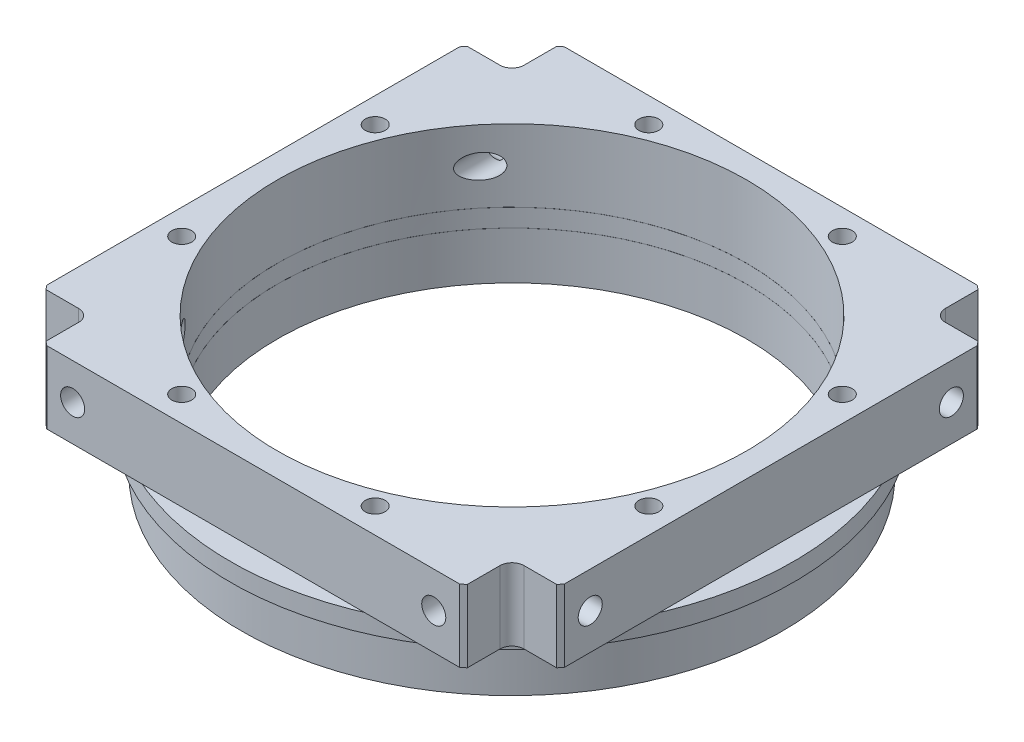
SolidWorks part; units mm, degrees
material "6061-T6 (SS)"
ref_plane "前视基准面" through (0, 0, 0) normal (0, 0, 1) x (1, 0, 0)
ref_plane "上视基准面" through (0, 0, 0) normal (0, 1, 0) x (1, 0, 0)
ref_plane "右视基准面" through (0, 0, 0) normal (1, 0, 0) x (0, 0, -1)
sketch "草图1" plane through (0, 0, 0) normal (0, 0, 1) x (1, 0, 0)
  line L0 (0, 0) -> (0, 30.5389) construction
  line L1 (-39, 0) -> (-45, 0)
  line L2 (-45, 0) -> (-45, 7.9)
  line L3 (-45, 7.9) -> (-46.8, 7.9)
  line L4 (-46.8, 7.9) -> (-46.8, 10.9)
  line L5 (-46.8, 10.9) -> (-55, 10.9)
  line L6 (-55, 10.9) -> (-55, 22.9)
  line L7 (-55, 22.9) -> (-39, 22.9)
  line L10 (-39, 22.9) -> (-39, 0)
  dimension "D1" = 90
  dimension "D2" = 78
  dimension "D3" = 7.9
  dimension "D4" = 1.8
  dimension "D5" = 3
  dimension "D6" = 110
  dimension "D9" = 12
revolve "旋转1" add sketch "草图1" angle 360 about L0
sketch "草图2" plane through (0, 22.9, 0) normal (0, 1, 0) x (1, 0, 0)
  line L1 (43, -43) -> (-43, -43)
  line L2 (43, -43) -> (43, 43)
  line L3 (43, 43) -> (-43, 43)
  line L4 (-43, -43) -> (-43, 43)
  line L5 (43, -43) -> (-43, 43) construction
  line L6 (43, 43) -> (-43, -43) construction
  point P0 (0, 0)
  dimension "D1" = 86
extrude "切除-拉伸1" cut sketch "草图2" against normal up to surface (12 mm away) flip side to cut up to face at (0, 10.9, -46.8)
sketch "草图4" plane through (0, 0, 43) normal (0, 0, 1) x (1, 0, 0)
  line L0 (-30, 16.9) -> (30, 16.9) construction
  line L1 (0, 16.9) -> (0, 0) construction
  line L3 (34.2929, 10.9) -> (18.4727, 10.9) construction
  circle A0 centre (-30, 16.9) radius 2
  circle A1 centre (30, 16.9) radius 2
  dimension "D3" = 4
  dimension "D1" = 6
  dimension "D2" = 60
extrude "切除-拉伸3" cut sketch "草图4" against normal through all
cosmetic thread "装饰螺纹线3" parameters "D2"=5
cosmetic thread "装饰螺纹线4" parameters "D2"=5
cosmetic thread "装饰螺纹线7" parameters "D2"=5
cosmetic thread "装饰螺纹线8" parameters "D2"=5
sketch "草图5" plane through (-43, 0, 0) normal (-1, 0, 0) x (0, 0, 1)
  line L0 (0, 0) -> (0, 16.9) construction
  line L1 (-30, 16.9) -> (30, 16.9) construction
  line L2 (34.2929, 10.9) -> (18.4727, 10.9) construction
  circle A0 centre (-30, 16.9) radius 2
  circle A1 centre (30, 16.9) radius 2
  dimension "D3" = 4
  dimension "D1" = 6
  dimension "D2" = 60
extrude "切除-拉伸4" cut sketch "草图5" against normal blind 12
cosmetic thread "装饰螺纹线5" parameters "D2"=5
cosmetic thread "装饰螺纹线6" parameters "D2"=5
extrude "切除-拉伸5" cut sketch "草图5<2>" along normal blind 12 from surface starting at face at (43, 14.9, 0)
sketch "草图5<2>" plane through (-43, 0, 0) normal (-1, 0, 0) x (0, 0, 1) same geometry as "草图5"
cosmetic thread "装饰螺纹线1" parameters "D2"=5
cosmetic thread "装饰螺纹线2" parameters "D2"=5
sketch "草图6" plane through (0, 0, 0) normal (0, -1, 0) x (1, 0, 0)
  line L0 (0, 0) -> (-16.0727, -38.8029) construction
  line L1 (0, 0) -> (0, -42) construction
  circle A0 centre (0, 0) radius 42 construction
  circle A1 centre (-16.0727, -38.8029) radius 1.65
  dimension "D1" = 84
  dimension "D2" = 3.3
  dimension "D3" = 22.5
extrude "切除-拉伸6" cut sketch "草图6" against normal blind 100
cosmetic thread "装饰螺纹线9" parameters "D2"=4
sketch "草图10" plane through (0, 0, 0) normal (0, -1, 0) x (1, 0, 0)
  circle A0 centre (-16.0727, -38.8029) radius 2.1
  dimension "D1" = 4.2
extrude "切除-拉伸8" cut sketch "草图10" against normal up to surface (10.9 mm away) up to face at (-35.3416, 10.9, -35.3416)
pattern_circular "阵列(圆周)1" count 8 over 360 about axis through (0, 0, 0) along (0, -1, 0) of "切除-拉伸6", "切除-拉伸8" reverse direction yes
sketch "草图7" plane through (0, 22.9, 0) normal (0, 1, 0) x (1, 0, 0)
  line L1 (35, -35) -> (-35, -35) construction
  line L2 (35, -35) -> (35, 35) construction
  line L3 (35, 35) -> (-35, 35) construction
  line L4 (-35, -35) -> (-35, 35) construction
  line L5 (35, -35) -> (-35, 35) construction
  line L6 (35, 35) -> (-35, -35) construction
  line L7 (-37, 35) -> (-53, 35)
  line L8 (-35, 37) -> (-35, 53)
  line L9 (-37, 55) -> (-53, 55)
  line L10 (-55, 37) -> (-55, 53)
  line L11 (37, 35) -> (53, 35)
  line L12 (35, 37) -> (35, 53)
  line L13 (37, 55) -> (53, 55)
  line L14 (55, 37) -> (55, 53)
  line L15 (37, -35) -> (53, -35)
  line L16 (35, -37) -> (35, -53)
  line L17 (37, -55) -> (53, -55)
  line L18 (55, -37) -> (55, -53)
  line L19 (-37, -35) -> (-53, -35)
  line L20 (-35, -37) -> (-35, -53)
  line L21 (-37, -55) -> (-53, -55)
  line L22 (-55, -37) -> (-55, -53)
  arc A0 (-53, -35) -> (-55, -37) centre (-53, -37) ccw
  arc A1 (-35, -53) -> (-37, -55) centre (-37, -53) cw
  arc A2 (-53, -55) -> (-55, -53) centre (-53, -53) cw
  arc A3 (53, -35) -> (55, -37) centre (53, -37) cw
  arc A4 (35, -53) -> (37, -55) centre (37, -53) ccw
  arc A5 (53, -55) -> (55, -53) centre (53, -53) ccw
  arc A6 (53, 35) -> (55, 37) centre (53, 37) ccw
  arc A7 (35, 53) -> (37, 55) centre (37, 53) cw
  arc A8 (53, 55) -> (55, 53) centre (53, 53) cw
  arc A9 (-53, 35) -> (-55, 37) centre (-53, 37) cw
  arc A10 (-35, 53) -> (-37, 55) centre (-37, 53) ccw
  arc A11 (-53, 55) -> (-55, 53) centre (-53, 53) ccw
  arc A12 (-37, -35) -> (-35, -37) centre (-37, -37) cw
  arc A13 (37, 35) -> (35, 37) centre (37, 37) cw
  arc A14 (35, -37) -> (37, -35) centre (37, -37) cw
  arc A15 (-35, 37) -> (-37, 35) centre (-37, 37) cw
  point P0 (0, 0)
  point P32 (55, 35)
  point P37 (55, 55)
  dimension "D3" = 2
  dimension "D1" = 70
  dimension "D2" = 20
extrude "切除-拉伸7" cut sketch "草图7" against normal blind 20
sketch "草图11" plane through (0, 0, 0) normal (1, 0, 0) x (0, 0, -1)
  line L0 (-45, 7.9) -> (45, 7.9) construction
  line L1 (-74.0955, 7.9) -> (62.1019, 7.9)
  line L2 (-74.0955, 7.9) -> (-74.0955, 7.89)
  line L3 (-74.0955, 7.89) -> (62.1019, 7.89)
  line L4 (62.1019, 7.9) -> (62.1019, 7.89)
  line L5 (-74.0955, 10.9) -> (62.1019, 10.9)
  line L6 (-74.0955, 10.9) -> (-74.0955, 10.89)
  line L7 (-74.0955, 10.89) -> (62.1019, 10.89)
  line L8 (62.1019, 10.9) -> (62.1019, 10.89)
  line L9 (18.4727, 10.9) -> (-18.4727, 10.9) construction
  dimension "D1" = 0.01
extrude "板材方案切割" cut sketch "草图11" against normal through all both and the other way through all
